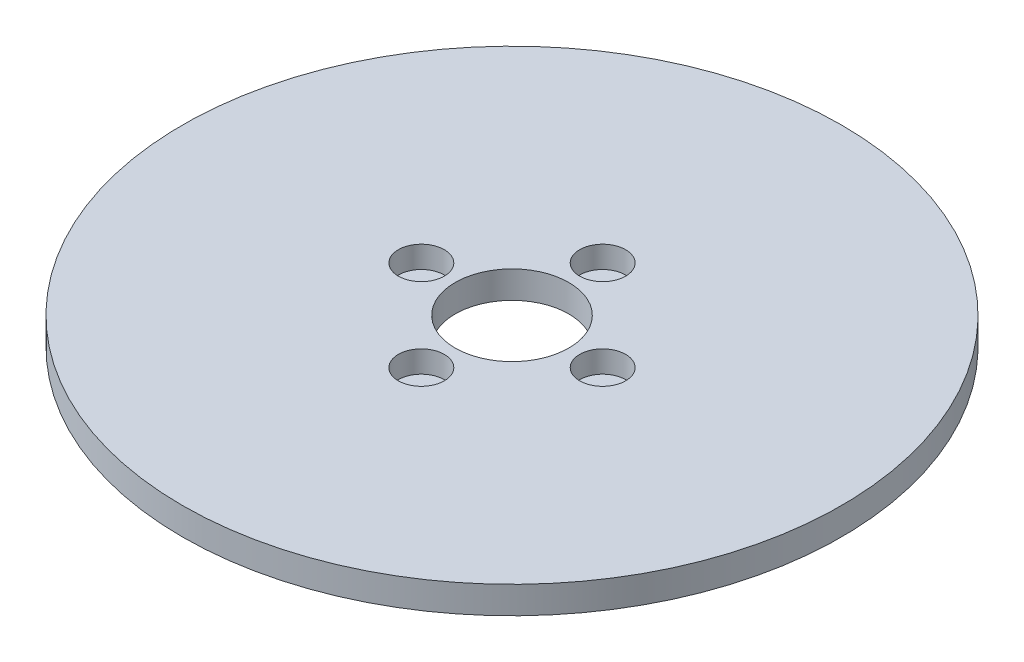
SolidWorks part; units mm, degrees
ref_plane "Front Plane" through (0, 0, 0) normal (0, 0, 1) x (1, 0, 0)
ref_plane "Top Plane" through (0, 0, 0) normal (0, 1, 0) x (1, 0, 0)
ref_plane "Right Plane" through (0, 0, 0) normal (1, 0, 0) x (0, 0, -1)
sketch "Sketch1" plane through (0, 0, 0) normal (0, 1, 0) x (1, 0, 0)
  circle A0 centre (0, 0) radius 72.5
  dimension "FLANGE_OD" = 145
extrude "Boss-Extrude1" add sketch "Sketch1" along normal blind 6
sketch "Sketch2" plane through (0, 0, 0) normal (0, 1, 0) x (1, 0, 0)
  circle A0 centre (0, 0) radius 12.5
  dimension "BORE_D" = 25
extrude "Cut-Extrude1" cut sketch "Sketch2" along normal through all
sketch "Sketch3" plane through (0, 6, 0) normal (0, 1, 0) x (1, 0, 0)
  circle A0 centre (0, 0) radius 19.9436 construction
  circle A1 centre (-19.9436, 0) radius 5.053
  dimension "BOLT_D" = 10.1061
  dimension "BOLT_PCD" = 39.8872
extrude "Cut-Extrude2" cut sketch "Sketch3" against normal blind 4.8269
pattern_circular "CirPattern1" count 4 over 360 about axis through (0, 0, 0) along (0, 1, 0) of "Cut-Extrude2"
